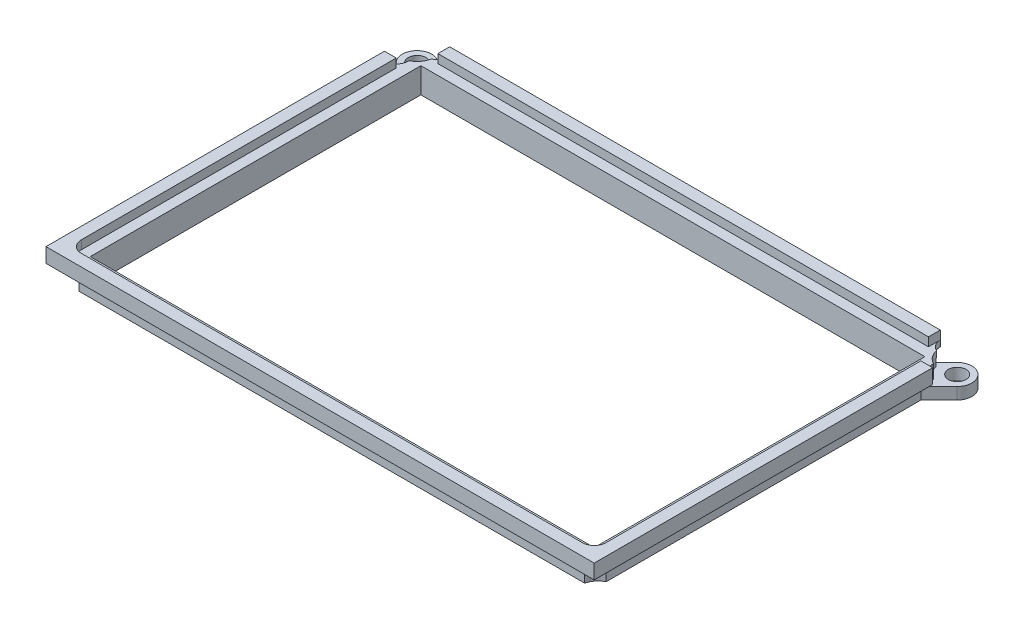
SolidWorks part; units mm, degrees
note: The reader was unsure of these and kept them because the rebuilt part matched: shared geometry of "Sketch1<3>", "Sketch1<4>", "Sketch1<5>", "Sketch2<3>".
ref_plane "Front Plane" through (0, 0, 0) normal (0, 0, 1) x (1, 0, 0)
ref_plane "Top Plane" through (0, 0, 0) normal (0, 1, 0) x (1, 0, 0)
ref_plane "Right Plane" through (0, 0, 0) normal (1, 0, 0) x (0, 0, -1)
sketch "Sketch1" plane through (0, 0, 0) normal (0, 1, 0) x (1, 0, 0)
  line L0 (-44.0665, 32.2478) -> (-41.6318, 29.813)
  line L1 (44.5196, -29.813) -> (-44.5196, -29.813)
  line L2 (44.5196, -29.813) -> (44.5196, 29.813)
  line L3 (44.5196, 29.813) -> (-44.5196, 29.813)
  line L4 (-44.5196, -29.813) -> (-44.5196, 29.813)
  line L5 (44.5196, -29.813) -> (-44.5196, 29.813) construction
  line L6 (44.5196, 29.813) -> (-44.5196, -29.813) construction
  line L7 (-47.6021, 28.7122) -> (-44.5196, 25.6298)
  line L8 (44.0665, 32.2478) -> (41.6318, 29.813)
  line L9 (47.6021, 28.7122) -> (44.5196, 25.6298)
  line L10 (46.5196, -31.813) -> (-46.5196, -31.813)
  line L11 (-46.5196, -31.813) -> (-46.5196, 25.6298)
  line L13 (46.5196, -31.813) -> (46.5196, 25.6298)
  line L14 (-44.5196, 25.6298) -> (-46.5196, 25.6298)
  line L15 (-42.7696, 28.063) -> (42.7696, 28.063)
  line L16 (-42.7696, 28.063) -> (-42.7696, -28.063)
  line L17 (-42.7696, -28.063) -> (42.7696, -28.063)
  line L18 (42.7696, 28.063) -> (42.7696, -28.063)
  line L19 (-42.7696, 28.063) -> (42.7696, -28.063) construction
  line L20 (-42.7696, -28.063) -> (42.7696, 28.063) construction
  line L21 (-41.6318, 29.813) -> (-41.6318, 31.813)
  line L22 (46.5196, 31.813) -> (-46.5196, 31.813) construction
  line L23 (-46.5196, -31.813) -> (-46.5196, 31.813) construction
  line L24 (41.6318, 29.813) -> (41.6318, 31.813)
  line L25 (44.5196, 25.6298) -> (46.5196, 25.6298)
  line L26 (41.6318, 31.813) -> (-41.6318, 31.813)
  line L27 (46.5196, -31.813) -> (46.5196, 31.813) construction
  circle A0 centre (-45.8343, 30.48) radius 1.5
  circle A1 centre (45.8343, 30.48) radius 1.5
  circle A2 centre (-45.8343, 30.48) radius 2.5
  circle A3 centre (45.8343, 30.48) radius 2.5
  point P0 (0, 0)
  point P24 (0, 0)
  dimension "D3" = 3
  dimension "D7" = 5
  dimension "D1" = 89.0392
  dimension "D2" = 59.626
  dimension "D4" = 1.3147
  dimension "D5" = 0.667
  dimension "D6" = 1.3147
  dimension "D8" = 45
  dimension "D10" = 56.126
  dimension "D11" = 85.5392
  dimension "D9" = 2
extrude "Boss-Extrude1" add sketch "Sketch1" along normal blind 2.4732
extrude "Boss-Extrude2" add sketch "Sketch1<3>" along normal blind 1 contours A3 L3 A2 L4 L1 L2 L15 L18 L17 L16
sketch "Sketch1<3>" plane through (0, 0, 0) normal (0, 1, 0) x (1, 0, 0) same geometry as "Sketch1"
extrude "Boss-Extrude3" add sketch "Sketch1<4>" against normal offset from surface (3.2902 mm away) 5.7634 contours A3 L3 A2 L4 L1 L2 L15 L18 L17 L16
sketch "Sketch1<4>" plane through (0, 0, 0) normal (0, 1, 0) x (1, 0, 0) same geometry as "Sketch1"
extrude "Boss-Extrude4" add sketch "Sketch1<5>" along normal blind 2 from surface at -3.2902 contours L3 A2 L4 A0 | A2 L7 L4 | A2 L3 L0 | L4 A2 L3 A0 | A3 L3 A1 L2 | A3 L8 L3 | A3 L2 L9 | L3 A3 L2 A1 starting at face at (0, -3.2902, 0)
sketch "Sketch1<5>" plane through (0, 0, 0) normal (0, 1, 0) x (1, 0, 0) same geometry as "Sketch1"
fillet "Fillet1" radius 2 4 edges at (44.5196, 0.5, -25.6298) (41.6318, 0.5, -29.813) (-41.6318, 0.5, -29.813) (-44.5196, 0.5, -25.6298)
fillet "Fillet2" radius 2 2 edges at (-44.5196, 1.7366, 29.813) (44.5196, 1.7366, 29.813)
sketch "Sketch2" plane through (0, -1.2902, 0) normal (0, 1, 0) x (1, 0, 0)
  circle A0 centre (-45.8343, 30.48) radius 3
  circle A1 centre (45.8343, 30.48) radius 3
  circle A2 centre (-45.8343, -30.48) radius 3
  circle A3 centre (45.8343, -30.48) radius 3
  point P10 (0, 0)
  point P11 (0, 0)
  point P12 (0, 0)
  point P13 (0, 0)
  line M5 (-43.4249, 29.813) -> (-41.6318, 29.813)
  line M6 (-41.6318, 29.813) -> (-44.0665, 32.2478)
  arc M7 (-44.0665, 32.2478) -> (-47.6021, 28.7122) centre (-45.8343, 30.48) ccw
  line M8 (-47.6021, 28.7122) -> (-44.5196, 25.6298)
  line M9 (-44.5196, 25.6298) -> (-44.5196, 28.3536)
  arc M10 (-44.5196, 28.3536) -> (-43.4249, 29.813) centre (-45.8343, 30.48) ccw
  circle M11 centre (-45.8343, 30.48) radius 1.5
  dimension "D2" = 6
  dimension "D1" = 60.96
extrude "Cut-Extrude1" cut sketch "Sketch2" along normal blind 3 contours A0 M6 M8 M7 | A0 M5 M6 M7 M8 M9 M10 M11 | A0 M9 M5 M10 | A1
extrude "Cut-Extrude2" cut sketch "Sketch2<3>" along normal blind 2.5 from surface at -2 contours A2 | A3 starting at face at (0, -3.2902, -17.6715)
sketch "Sketch2<3>" plane through (0, -1.2902, 0) normal (0, 1, 0) x (1, 0, 0) same geometry as "Sketch2"
equation "\"D6@Sketch1\"=\"D4@Sketch1\""
